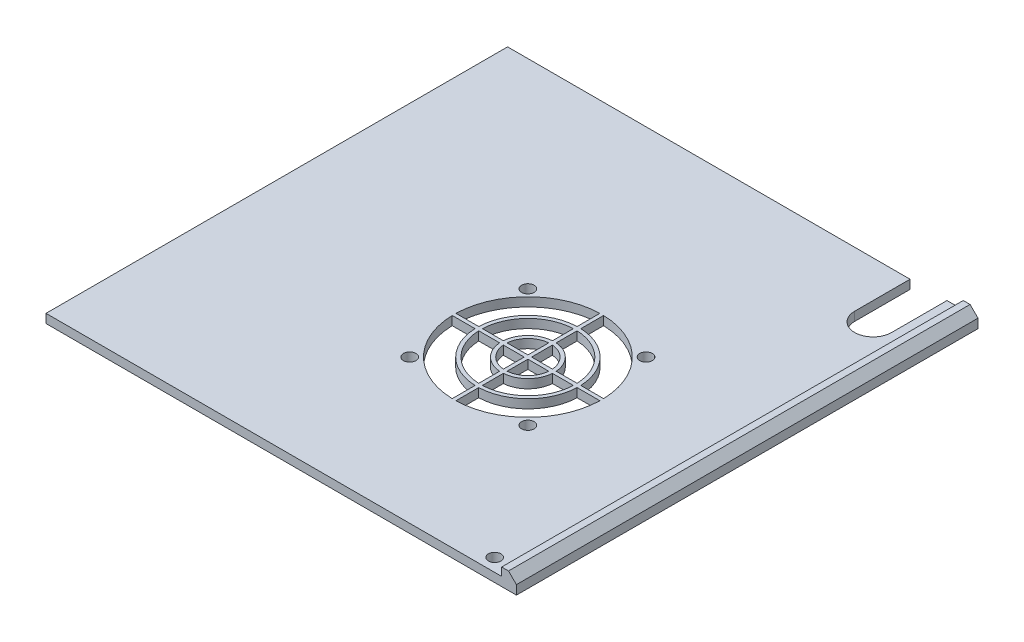
SolidWorks part; units mm, degrees
material "ABS"
ref_plane "Front Plane" through (0, 0, 0) normal (0, 0, 1) x (1, 0, 0)
ref_plane "Top Plane" through (0, 0, 0) normal (0, 1, 0) x (1, 0, 0)
ref_plane "Right Plane" through (0, 0, 0) normal (1, 0, 0) x (0, 0, -1)
ref_axis "Axis1" through (0, 0, 55) along (0, 0, -1)
sketch "Sketch1" plane through (0, 0, 0) normal (0, 1, 0) x (1, 0, 0)
  line L1 (-60.75, 62.5) -> (60.75, 62.5)
  line L2 (-60.75, 62.5) -> (-60.75, -62.5)
  line L3 (-60.75, -62.5) -> (60.75, -62.5)
  line L4 (60.75, 62.5) -> (60.75, -62.5)
  line L5 (-60.75, 62.5) -> (60.75, -62.5) construction
  line L6 (-60.75, -62.5) -> (60.75, 62.5) construction
  point P0 (0, 0)
  dimension "D1" = 121.5
  dimension "D2" = 125
extrude "Boss-Extrude1" add sketch "Sketch1" along normal blind 2.4
sketch "4040-extrusion" plane through (0, 0, 62.5) normal (0, 0, 1) x (1, 0, 0)
  line L0 (60.75, 0) -> (60.75, 9.5) construction
  line L1 (60.75, 9.5) -> (60.75, 4.3) construction
  line L2 (60.75, 4.3) -> (62.55, 2.5) construction
  line L3 (62.55, 2.5) -> (62.55, 4.71) construction
  line L4 (62.55, 4.71) -> (64.55, 4.71) construction
  line L5 (64.55, 4.71) -> (66.75, 2.5118) construction
  line L6 (66.75, 2.5118) -> (66.75, 0) construction
  dimension "D1" = 9.5
  dimension "D2" = 5.2
  dimension "D3" = 7
  dimension "D4" = 1.8
  dimension "D5" = 2
  dimension "D6" = 3.11
  dimension "D7" = 2.21
  dimension "D8" = 6
sketch "Sketch3" plane through (0, 0, 62.5) normal (0, 0, 1) x (1, 0, 0)
  line L0 (60.75, 0) -> (60.75, 2.4)
  line L1 (60.75, 2.4) -> (62.55, 2.4)
  line L2 (62.55, 2.4) -> (62.55, 4.71) construction
  line L3 (62.55, 4.71) -> (64.55, 4.71) construction
  line L4 (64.55, 4.71) -> (66.75, 2.5118) construction
  line L5 (66.75, 2.5118) -> (66.75, 0) construction
  line L6 (66.75, 0) -> (66.65, 0) construction
  line L7 (62.65, 2.4) -> (62.65, 4.61)
  line L8 (62.65, 4.61) -> (64.5086, 4.61)
  line L9 (64.5086, 4.61) -> (66.65, 2.4704)
  line L10 (66.65, 2.4704) -> (66.65, 0)
  line L11 (62.55, 2.4) -> (62.65, 2.4)
  line L12 (66.65, 0) -> (60.75, 0)
  dimension "D1" = 0.1
extrude "Boss-Extrude2" add sketch "Sketch3" against normal up to surface (125 mm away) up to face at (0, 1.2, -62.5)
sketch "Sketch4" plane through (0, 2.4, 0) normal (0, 1, 0) x (1, 0, 0)
  line L0 (-60.75, -62.5) -> (62.65, -62.5) construction
  line L1 (53.75, -62.5) -> (60.75, -62.5) construction
  line L2 (53.75, -62.5) -> (53.75, -55.5) construction
  line L3 (53.75, -55.5) -> (60.75, -55.5) construction
  line L4 (60.75, -62.5) -> (60.75, -55.5) construction
  line L5 (53.75, -62.5) -> (60.75, -55.5) construction
  line L6 (53.75, -55.5) -> (60.75, -62.5) construction
  line L7 (57.25, -59) -> (62.65, -59) construction
  line L9 (62.65, 62.5) -> (62.65, -62.5) construction
  circle A0 centre (57.25, -59) radius 1.7
  point P4 (57.25, -59)
  dimension "D2" = 3.4
  dimension "D1" = 7
  dimension "D3" = 5.4
extrude "Cut-Extrude1" cut sketch "Sketch4" against normal through all
sketch "Sketch5" plane through (0, 2.4, 0) normal (0, 1, 0) x (1, 0, 0)
  line L0 (53.25, 62.5) -> (53.25, 47.5) construction
  line L1 (62.65, 62.5) -> (-60.75, 62.5) construction
  line L2 (58.25, 62.5) -> (58.25, 47.5)
  line L3 (48.25, 62.5) -> (48.25, 47.5)
  line L4 (53.25, 55) -> (62.65, 55) construction
  line L6 (48.25, 62.5) -> (58.25, 62.5)
  line L7 (62.65, 62.5) -> (62.65, -62.5) construction
  arc A0 (58.25, 62.5) -> (48.25, 62.5) centre (53.25, 62.5) ccw
  arc A1 (48.25, 47.5) -> (58.25, 47.5) centre (53.25, 47.5) ccw
  point P4 (53.25, 55)
  line M7 (62.65, 62.5) -> (-60.75, 62.5)
  dimension "D1" = 15
  dimension "D2" = 5
  dimension "D3" = 9.4
extrude "Cut-Extrude2" cut sketch "Sketch5" against normal through all contours L3 A1 L2 M7 region at (53.25, 2.4, -53.0036)
sketch "Sketch6" plane through (0, 2.4, 0) normal (0, 1, 0) x (1, 0, 0)
  line L0 (14.75, -7.5) -> (14.75, -62.5) construction
  line L1 (-5.25, 12.5) -> (34.75, 12.5) construction
  line L2 (-5.25, 12.5) -> (-5.25, -27.5) construction
  line L3 (-5.25, -27.5) -> (34.75, -27.5) construction
  line L4 (34.75, 12.5) -> (34.75, -27.5) construction
  line L5 (-5.25, 12.5) -> (34.75, -27.5) construction
  line L6 (-5.25, -27.5) -> (34.75, 12.5) construction
  line L7 (-60.75, -62.5) -> (60.75, -62.5) construction
  line L8 (14.75, -7.5) -> (60.75, -7.5) construction
  line L9 (60.75, 62.5) -> (60.75, -62.5) construction
  line L11 (-1.25, 8.5) -> (30.75, 8.5) construction
  line L12 (-1.25, 8.5) -> (-1.25, -23.5) construction
  line L13 (-1.25, -23.5) -> (30.75, -23.5) construction
  line L14 (30.75, 8.5) -> (30.75, -23.5) construction
  line L15 (-1.25, 8.5) -> (30.75, -23.5) construction
  line L16 (-1.25, -23.5) -> (30.75, 8.5) construction
  circle A0 centre (-1.25, -23.5) radius 1.7
  circle A1 centre (30.75, -23.5) radius 1.7
  circle A2 centre (30.75, 8.5) radius 1.7
  circle A3 centre (-1.25, 8.5) radius 1.7
  circle A4 centre (14.75, -7.5) radius 20 construction
  point P0 (14.75, -7.5)
  dimension "D4" = 3.4
  dimension "D1" = 46
  dimension "D2" = 55
  dimension "D3" = 40
  dimension "D5" = 32
extrude "Cut-Extrude3" cut sketch "Sketch6" against normal through all
sketch "Sketch7" plane through (0, 2.4, 0) normal (0, 1, 0) x (1, 0, 0)
  line L0 (14.7563, -7.5) -> (14.7563, 12.4937) construction
  line L1 (14.7563, -7.5) -> (21.4208, -7.5) construction
  line L2 (21.4208, -7.5) -> (28.0854, -7.5) construction
  line L3 (28.0854, -7.5) -> (34.75, -7.5) construction
  line L4 (28.0854, -7) -> (34.75, -7)
  line L5 (21.4208, -7) -> (28.0854, -7)
  line L6 (15.2563, -7) -> (21.4208, -7)
  line L7 (15.2563, -7) -> (15.2563, 12.4937)
  line L8 (34.75, 12.5) -> (34.75, -27.5) construction
  line L9 (14.75, -7.5) -> (60.75, -7.5) construction
  arc A2 (14.7563, -0.8354) -> (21.4208, -7.5) centre (14.7563, -7.5) cw construction
  arc A3 (14.7563, 5.8292) -> (28.0854, -7.5) centre (14.7563, -7.5) cw construction
  arc A4 (14.7563, -1.3354) -> (20.9208, -7.5) centre (14.7563, -7.5) cw
  arc A5 (14.7563, 5.3292) -> (27.5854, -7.5) centre (14.7563, -7.5) cw
  arc A6 (14.7563, -0.3354) -> (21.9208, -7.5) centre (14.7563, -7.5) cw
  arc A7 (14.7563, 6.3292) -> (28.5854, -7.5) centre (14.7563, -7.5) cw
  arc A8 (15.2563, 12.4937) -> (34.75, -7) centre (14.7563, -7.5) cw
  circle A9 centre (14.75, -7.5) radius 20 construction
  arc A10 (14.7563, -1.3354) -> (20.9208, -7.5) centre (14.7563, -7.5) cw construction
  dimension "D1" = 0.5
  dimension "D2" = 0.5
  dimension "D3" = 0.5
extrude "Cut-Extrude4" cut sketch "Sketch7" against normal through all contours A4 L7 L6 | L7 A6 L5 A5 | A8 L7 A7 L4 region at (25.7341, 2.4, -3.4778) region at (21.3869, 2.4, 0.8693) region at (17.5927, 2.4, 4.6635)
pattern_circular "CirPattern1" count 4 every 90 about axis through (14.7563, 0, 7.5) along (0, 1, 0) of "Cut-Extrude4"
